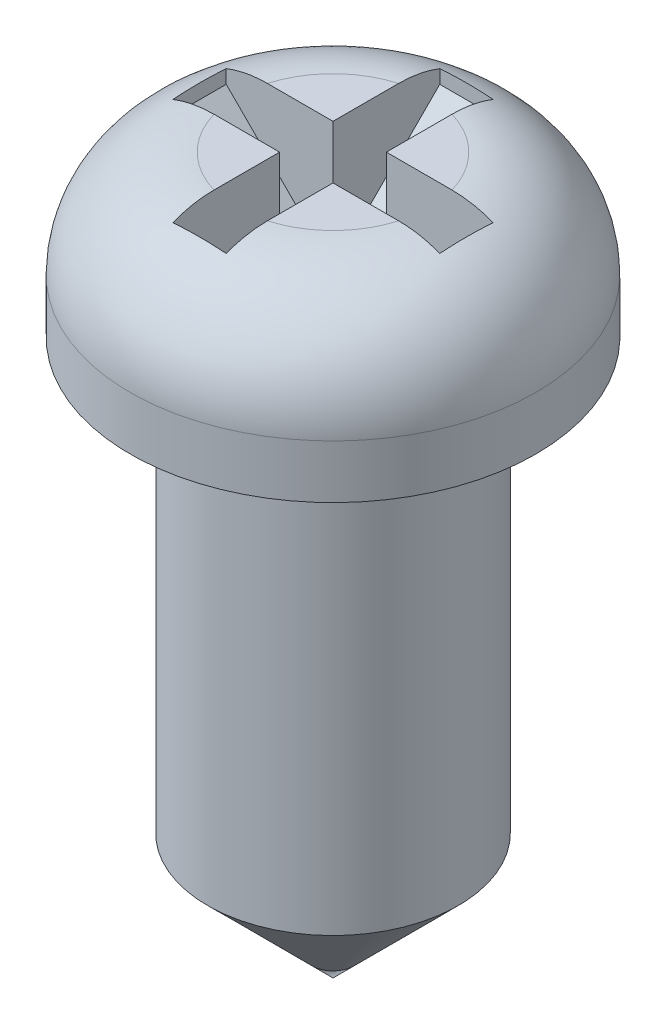
SolidWorks part; units mm, degrees
material "AISI 304"
ref_plane "Front Plane" through (0, 0, 0) normal (0, 0, 1) x (1, 0, 0)
ref_plane "Top Plane" through (0, 0, 0) normal (0, 1, 0) x (1, 0, 0)
ref_plane "Right Plane" through (0, 0, 0) normal (1, 0, 0) x (0, 0, -1)
ref_axis "X-Axis" through (-88.99, 0, 0) along (1, 0, 0)
ref_axis "Y-Axis" through (0, 0, -88.99) along (0, 0, 1)
ref_axis "Z-Axis" through (0, 55, 0) along (0, -1, 0)
sketch "Sketch1" plane through (0, 0, 0) normal (0, 0, 1) x (1, 0, 0)
  line L0 (1.175, 0) -> (1.9, 0)
  line L1 (1.9, 0) -> (1.9, 0.5)
  line L2 (0.9, 1.5) -> (0, 1.5)
  line L3 (0, 1.5) -> (0, -5.2)
  line L4 (1.175, 0) -> (1.175, -4.025)
  line L5 (1.175, -4.025) -> (0, -5.2)
  line L6 (0, -5.2) -> (0, -11.9) construction
  arc A0 (1.9, 0.5) -> (0.9, 1.5) centre (0.9, 0.5) ccw
  dimension "D6" = 1
  dimension "D1" = 45
  dimension "D2" = 3.8
  dimension "D3" = 2.35
  dimension "D4" = 5.2
  dimension "D5" = 1.5
revolve "Revolve1" add sketch "Sketch1" angle 360 about L6
sketch "Sketch2" plane through (0, 1.5, 0) normal (0, 1, 0) x (1, 0, 0)
  line L0 (0.25, 0.25) -> (1.25, 0.25)
  line L1 (-1.25, 0.25) -> (-0.25, 0.25)
  line L2 (-1.25, 0.25) -> (-1.25, -0.25)
  line L3 (-1.25, -0.25) -> (-0.25, -0.25)
  line L4 (1.25, 0.25) -> (1.25, -0.25)
  line L5 (-0.25, 1.25) -> (0.25, 1.25)
  line L6 (-0.25, 1.25) -> (-0.25, 0.25)
  line L7 (-0.25, -1.25) -> (0.25, -1.25)
  line L8 (0.25, 1.25) -> (0.25, 0.25)
  line L9 (0.25, -0.25) -> (0.25, -1.25)
  line L10 (-0.25, -0.25) -> (-0.25, -1.25)
  line L11 (0.25, -0.25) -> (1.25, -0.25)
  line L12 (0.25, 0.25) -> (-0.25, -0.25) construction
  dimension "D1" = 0.5
  dimension "D2" = 2.5
extrude "Cut-Extrude1" cut sketch "Sketch2" against normal blind 1
chamfer "Chamfer1" distance 0.8 angle 45 4 edges at (1.25, 0.5, 0) (0, 0.5, 1.25) (-1.25, 0.5, 0) (0, 0.5, -1.25)
